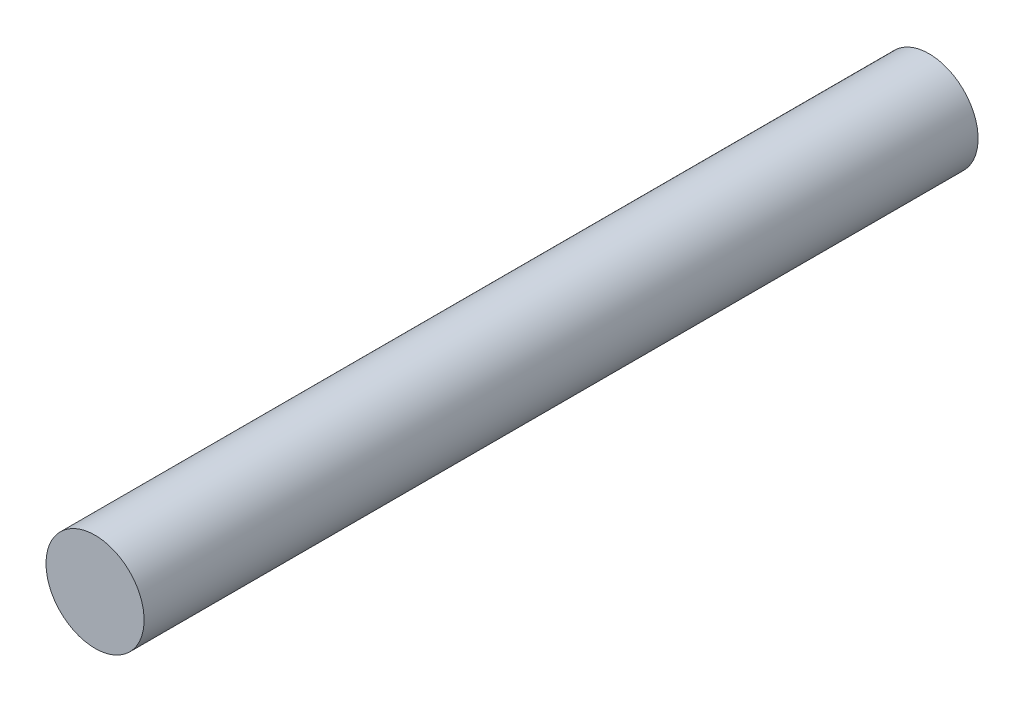
SolidWorks part; units mm, degrees
material "Hexcel AS4C (3000 Filaments)"
ref_plane "Front" through (0, 0, 0) normal (0, 0, 1) x (1, 0, 0)
ref_plane "Top" through (0, 0, 0) normal (0, 1, 0) x (1, 0, 0)
ref_plane "Right" through (0, 0, 0) normal (1, 0, 0) x (0, 0, -1)
sketch "Sketch1" plane through (0, 0, 0) normal (0, 0, 1) x (1, 0, 0)
  circle A0 centre (0, 0) radius 3.175
  dimension "D1" = 6.35
extrude "Boss-Extrude1" add sketch "Sketch1" along normal blind 53.975
equation "\"truss_member_od\" = .25in"
equation "\"truss_member_L1\" = 2.125in"
equation "\"connector_hole_depth\" = .375in"
equation "\"truss_member_L2\" = 3in"
equation "\"D1@Boss-Extrude1\"=\"truss_member_L1\""
equation "\"D1@Sketch1\"=\"truss_member_od\""
